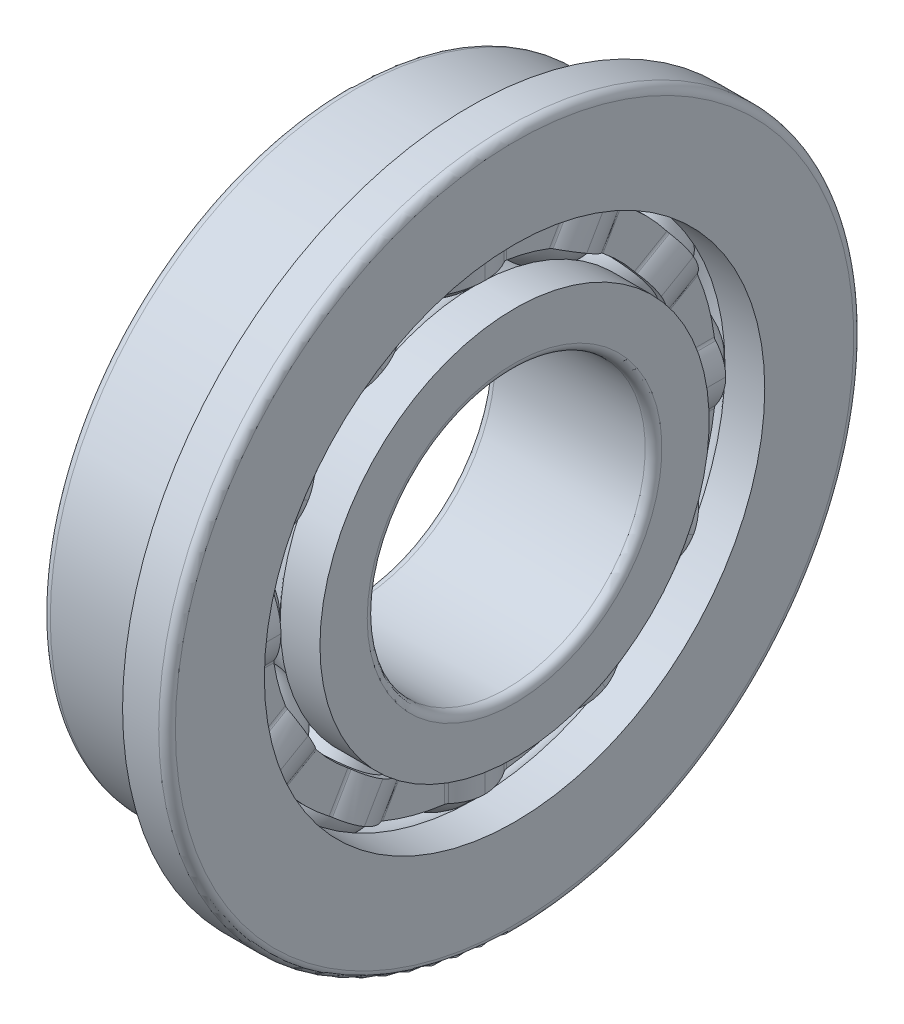
SolidWorks part; units mm, degrees
ref_plane "Front" through (0, 0, 0) normal (0, 0, 1) x (1, 0, 0)
ref_plane "Top" through (0, 0, 0) normal (0, 1, 0) x (1, 0, 0)
ref_plane "Right" through (0, 0, 0) normal (1, 0, 0) x (0, 0, -1)
sketch "Support-Front-Body" plane through (0, 0, 0) normal (0, 0, 1) x (1, 0, 0)
  line L0 (-1.5, 0) -> (1.5, 0) construction
  line L1 (1.5, 0) -> (1.5, 2.5) construction
  line L2 (-1.5, 0) -> (-1.5, 2.5) construction
  line L4 (-1.5, 5.5) -> (1.5, 5.5)
  line L5 (-1.5, 5.5) -> (-1.5, 4.5)
  line L6 (-1.5, 4.5) -> (1.5, 4.5)
  line L7 (1.5, 6.25) -> (1.5, 4.5)
  line L8 (-1.5, 3.5) -> (1.5, 3.5)
  line L9 (-1.5, 3.5) -> (-1.5, 2.5)
  line L10 (-1.5, 2.5) -> (1.5, 2.5)
  line L11 (1.5, 3.5) -> (1.5, 2.5)
  line L13 (-1.5, 4) -> (1.5, 4) construction
  line L14 (0, 0) -> (0, 2.5) construction
  line L15 (0, 2.5) -> (0, 3.5) construction
  line L16 (0, 3.5) -> (0, 4.5) construction
  line L17 (0, 4.5) -> (0, 5.5) construction
  line L19 (0.7, 6.25) -> (1.5, 6.25)
  line L20 (0.7, 6.25) -> (0.7, 5.5)
  dimension "Diam-Inner" = 5
  dimension "Diam-Outer" = 11
  dimension "CC-Ball" = 8
  dimension "Width-Inner" = 3
  dimension "Diam-Flange" = 12.5
  dimension "Width-Flange" = 0.8
sketch "Support-Front-Ball" plane through (0, 0, 0) normal (0, 0, 1) x (1, 0, 0)
  line L0 (-0.9, 4) -> (0.9, 4) construction
  line L1 (0, 0) -> (0, 3.1) construction
  line L2 (-1.5, 4) -> (1.5, 4) construction
  line L3 (0, 4) -> (0, 4.9) construction
  line L6 (0, 3.1) -> (0, 4) construction
  circle A0 centre (0, 4) radius 0.9
  dimension "Diam-Ball" = 1.8
sketch "Support-Front-Groove" plane through (0, 0, 0) normal (0, 0, 1) x (1, 0, 0)
  line L0 (0, 4.5) -> (0, 4.3333) construction
  line L1 (0, 4.3333) -> (0, 4.1667) construction
  line L2 (0, 4.1667) -> (0, 4) construction
  line L3 (-1.5, 4) -> (1.5, 4) construction
  line L4 (-0.9, 4) -> (0.9, 4) construction
  line L6 (-1.5, 4.5) -> (1.5, 4.5) construction
  line L7 (0, 3.1367) -> (0, 3.1) construction
  line L8 (0.7483, 3.5) -> (0.7851, 3.5) construction
  line L9 (-1.5, 3.5) -> (1.5, 3.5) construction
  line L11 (0, 0) -> (0, 3.1) construction
  line L12 (-0.9, 4) -> (0.9, 4) construction
  circle A0 centre (0, 4) radius 0.9 construction
  circle A1 centre (0, 4.1667) radius 1.0299
  circle A2 centre (0, 3.8333) radius 1.0299
sketch "Support-Front-Ball-Cage" plane through (0, 0, 0) normal (0, 0, 1) x (1, 0, 0)
  line L0 (0.9, 4) -> (-0.9644, 4) construction
  line L1 (-0.9644, 4.3333) -> (0.9644, 4.3333)
  line L2 (-0.9644, 4.3333) -> (-0.9644, 3.6667)
  line L3 (-0.9644, 3.6667) -> (0.9644, 3.6667)
  line L4 (0.9644, 4.3333) -> (0.9644, 3.6667)
  line L5 (-1.5, 4) -> (1.5, 4) construction
  line L6 (0, 3.6667) -> (0, 4.3333) construction
  line L7 (0, 3.5) -> (0, 4.5) construction
  line L8 (0.9, 4) -> (0.9644, 4) construction
  line L9 (0.9322, 4) -> (0.9322, 4.1667) construction
  line L10 (0.9322, 4.1667) -> (0.9322, 4.3333) construction
  line L11 (0.9322, 4.3333) -> (0.9322, 4.5) construction
  line L12 (-1.5, 4.5) -> (1.5, 4.5) construction
  line L13 (0.9644, 4.4167) -> (0.7977, 4.4167) construction
  line L14 (0, 4.3333) -> (0, 4.9644) construction
  circle A0 centre (0, 4) radius 0.9 construction
  circle A1 centre (0, 4) radius 0.9644 construction
  point P26 (0.9322, 4.4167)
sketch "Support-Right-Ball-Cage" plane through (0, 0, 0) normal (1, 0, 0) x (0, 0, -1)
  line L0 (0, 0) -> (0, 5.5) construction
  line L1 (0, 0) -> (-2.75, 4.7631) construction
  line L2 (0, 3.0356) -> (-1.5178, 2.6289) construction
  line L3 (-2.4822, 4.2993) -> (0, 4.9644) construction
  line L4 (0, 0) -> (-1.5205, 5.2857) construction
  line L6 (-1.3261, 5.3377) -> (0, 0) construction
  circle A0 centre (0, 0) radius 3.6667
  circle A1 centre (0, 0) radius 4.3333
  circle A2 centre (0, 4) radius 0.9644
  circle A3 centre (0, 0) radius 4 construction
  circle A4 centre (-2, 3.4641) radius 0.9644
  dimension "Angle-Ball" = 30
ref_plane "Ref-Plane-1" through (0, 2.8322, 0.7589) normal (0, 0.9659, 0.2588) x (-1, 0, 0)
sketch "Support-Ball-Gage-Inner" plane through (0, 2.8322, 0.7589) normal (0, 0.9659, 0.2588) x (-1, 0, 0)
  line L0 (-0.7955, -0.209) -> (-0.7955, 0.209)
  line L1 (0.7955, -0.209) -> (0.7955, 0.209)
  line L2 (0.9644, 0.7857) -> (0.9644, -0.7857)
  line L3 (-0.9644, 0) -> (-0.7955, 0) construction
  line L4 (-0.9, -1.0353) -> (-0.9, -0.209) construction
  line L5 (-0.9, -0.209) -> (-0.7955, -0.209) construction
  line L6 (-0.9, -0.209) -> (-0.9, -0.1045) construction
  line L7 (-0.9, -0.1045) -> (-0.9, 0) construction
  line L8 (-0.7955, 0) -> (0, 0) construction
  line L9 (-0.9644, 0.7857) -> (-0.9644, -0.7857)
  line L10 (-0.9644, -1.1215) -> (-0.9644, -0.949) construction
  line L11 (-0.9, -0.1045) -> (-0.7955, -0.209) construction
  line L12 (0, 0.7857) -> (0, -0.7857) construction
  arc A0 (-0.9644, -0.7857) -> (-0.812, -0.2654) centre (0, -0.7857) cw
  arc A1 (-0.812, -0.2654) -> (-0.7955, -0.209) centre (-0.9, -0.209) ccw
  arc A2 (-0.7955, 0.209) -> (-0.812, 0.2654) centre (-0.9, 0.209) ccw
  arc A3 (-0.812, 0.2654) -> (-0.9644, 0.7857) centre (0, 0.7857) cw
  arc A4 (0.812, 0.2654) -> (0.9644, 0.7857) centre (0, 0.7857) ccw
  arc A5 (0.7955, 0.209) -> (0.812, 0.2654) centre (0.9, 0.209) cw
  arc A6 (0.812, -0.2654) -> (0.7955, -0.209) centre (0.9, -0.209) cw
  arc A7 (0.9644, -0.7857) -> (0.812, -0.2654) centre (0, -0.7857) ccw
  dimension "D1" = 45
ref_plane "Ref-Plane-2" through (0, 4.6319, 1.2411) normal (0, -0.9659, -0.2588) x (1, 0, 0)
sketch "Support-Ball-Gage-Outer" plane through (0, 4.6319, 1.2411) normal (0, -0.9659, -0.2588) x (1, 0, 0)
  line L0 (0.9644, 1.2849) -> (0.9644, -1.2849)
  line L1 (0.7955, -0.7082) -> (0.7955, 0.7082)
  line L2 (0.9644, 0.7857) -> (0.9644, -0.7857) construction
  line L7 (0.7955, -0.209) -> (0.7955, 0.209) construction
  line L8 (0, 1.2849) -> (0, -1.2849) construction
  line L9 (-0.9644, 1.2849) -> (-0.9644, -1.2849)
  line L10 (-0.7955, -0.7082) -> (-0.7955, 0.7082)
  arc A0 (0.9644, -1.2849) -> (0.812, -0.7646) centre (0, -1.2849) ccw
  arc A1 (0.812, -0.7646) -> (0.7955, -0.7082) centre (0.9, -0.7082) cw
  arc A2 (0.7955, 0.7082) -> (0.812, 0.7646) centre (0.9, 0.7082) cw
  arc A3 (0.812, 0.7646) -> (0.9644, 1.2849) centre (0, 1.2849) ccw
  arc A4 (0.812, 0.2654) -> (0.7955, 0.209) centre (0.9, 0.209) ccw construction
  arc A5 (-0.812, -0.7646) -> (-0.7955, -0.7082) centre (-0.9, -0.7082) ccw
  arc A6 (-0.9644, -1.2849) -> (-0.812, -0.7646) centre (0, -1.2849) cw
  arc A7 (-0.812, 0.7646) -> (-0.9644, 1.2849) centre (0, 1.2849) cw
  arc A8 (-0.7955, 0.7082) -> (-0.812, 0.7646) centre (-0.9, 0.7082) ccw
ref_axis "Ref-Axis" through (-1.1, 0, 0) along (1, 0, 0)
ref_plane "Ref-Plane-Right" through (1.5, 0, 0) normal (1, 0, 0) x (0, 0, -1)
ref_plane "Ref-Plane-Left" through (-1.5, 0, 0) normal (1, 0, 0) x (0, 0, -1)
sketch "Sketch7" plane through (0, 0, 0) normal (0, 0, 1) x (1, 0, 0)
  line L0 (-0.9, 4) -> (0.9, 4) construction
  line L2 (-0.9, 4) -> (0.9, 4) construction
  line L4 (-0.9, 4) -> (0.9, 4)
  circle A0 centre (0, 4) radius 0.9 construction
  arc A1 (-0.9, 4) -> (0.9, 4) centre (0, 4) ccw
revolve "Body-Ball" add sketch "Sketch7" angle 360 about L2
sketch "Sketch10" plane through (0, 0, 0) normal (0, 0, 1) x (1, 0, 0)
  line L0 (-1.5, 0) -> (1.5, 0) construction
  line L1 (-0.9644, 4.3333) -> (-0.9644, 3.6667) construction
  line L2 (-0.9644, 4.3333) -> (0.9644, 4.3333) construction
  line L3 (0.9644, 4.3333) -> (0.9644, 3.6667) construction
  line L4 (-0.9644, 3.6667) -> (0.9644, 3.6667) construction
  line L5 (-1.5, 0) -> (1.5, 0) construction
  line L6 (-0.9644, 4.3333) -> (-0.9644, 3.6667)
  line L7 (-0.9644, 4.3333) -> (0.9644, 4.3333)
  line L8 (0.9644, 4.3333) -> (0.9644, 3.6667)
  line L9 (-0.9644, 3.6667) -> (0.9644, 3.6667)
revolve "Body-Ball-Cage" add sketch "Sketch10" angle 360 about L5
sketch "Sketch16" plane through (0, 2.8322, 0.7589) normal (0, 0.9659, 0.2588) x (-1, 0, 0)
  line L0 (0.7955, -0.209) -> (0.7955, 0.209) construction
  line L1 (0.9644, 0.7857) -> (0.9644, -0.7857) construction
  line L2 (0.7955, -0.209) -> (0.7955, 0.209)
  line L3 (0.9644, 0.7857) -> (0.9644, -0.7857)
  arc A0 (0.812, 0.2654) -> (0.9644, 0.7857) centre (0, 0.7857) ccw construction
  arc A1 (0.812, 0.2654) -> (0.7955, 0.209) centre (0.9, 0.209) ccw construction
  arc A2 (0.7955, -0.209) -> (0.812, -0.2654) centre (0.9, -0.209) ccw construction
  arc A3 (0.9644, -0.7857) -> (0.812, -0.2654) centre (0, -0.7857) ccw construction
  arc A4 (0.812, 0.2654) -> (0.9644, 0.7857) centre (0, 0.7857) ccw
  arc A5 (0.812, 0.2654) -> (0.7955, 0.209) centre (0.9, 0.209) ccw
  arc A6 (0.7955, -0.209) -> (0.812, -0.2654) centre (0.9, -0.209) ccw
  arc A7 (0.9644, -0.7857) -> (0.812, -0.2654) centre (0, -0.7857) ccw
sketch "Sketch17" plane through (0, 4.6319, 1.2411) normal (0, -0.9659, -0.2588) x (1, 0, 0)
  line L0 (-0.7955, -0.7082) -> (-0.7955, 0.7082) construction
  line L1 (-0.9644, 1.2849) -> (-0.9644, -1.2849) construction
  line L2 (-0.7955, -0.7082) -> (-0.7955, 0.7082)
  line L3 (-0.9644, 1.2849) -> (-0.9644, -1.2849)
  arc A0 (-0.9644, 1.2849) -> (-0.812, 0.7646) centre (0, 1.2849) ccw construction
  arc A1 (-0.7955, 0.7082) -> (-0.812, 0.7646) centre (-0.9, 0.7082) ccw construction
  arc A2 (-0.812, -0.7646) -> (-0.7955, -0.7082) centre (-0.9, -0.7082) ccw construction
  arc A3 (-0.812, -0.7646) -> (-0.9644, -1.2849) centre (0, -1.2849) ccw construction
  arc A4 (-0.9644, 1.2849) -> (-0.812, 0.7646) centre (0, 1.2849) ccw
  arc A5 (-0.7955, 0.7082) -> (-0.812, 0.7646) centre (-0.9, 0.7082) ccw
  arc A6 (-0.812, -0.7646) -> (-0.7955, -0.7082) centre (-0.9, -0.7082) ccw
  arc A7 (-0.812, -0.7646) -> (-0.9644, -1.2849) centre (0, -1.2849) ccw
loft "Cut-Ball-Cage-1" cut profiles "Sketch16", "Sketch17"
sketch "Sketch14" plane through (0, 2.8322, 0.7589) normal (0, 0.9659, 0.2588) x (-1, 0, 0)
  line L0 (-0.7955, -0.209) -> (-0.7955, 0.209) construction
  line L1 (-0.9644, 0.7857) -> (-0.9644, -0.7857) construction
  line L2 (-0.7955, -0.209) -> (-0.7955, 0.209)
  line L3 (-0.9644, 0.7857) -> (-0.9644, -0.7857)
  arc A0 (-0.9644, 0.7857) -> (-0.812, 0.2654) centre (0, 0.7857) ccw construction
  arc A1 (-0.7955, 0.209) -> (-0.812, 0.2654) centre (-0.9, 0.209) ccw construction
  arc A2 (-0.812, -0.2654) -> (-0.7955, -0.209) centre (-0.9, -0.209) ccw construction
  arc A3 (-0.812, -0.2654) -> (-0.9644, -0.7857) centre (0, -0.7857) ccw construction
  arc A4 (-0.9644, 0.7857) -> (-0.812, 0.2654) centre (0, 0.7857) ccw
  arc A5 (-0.7955, 0.209) -> (-0.812, 0.2654) centre (-0.9, 0.209) ccw
  arc A6 (-0.812, -0.2654) -> (-0.7955, -0.209) centre (-0.9, -0.209) ccw
  arc A7 (-0.812, -0.2654) -> (-0.9644, -0.7857) centre (0, -0.7857) ccw
sketch "Sketch15" plane through (0, 4.6319, 1.2411) normal (0, -0.9659, -0.2588) x (1, 0, 0)
  line L0 (0.7955, -0.7082) -> (0.7955, 0.7082) construction
  line L1 (0.9644, 1.2849) -> (0.9644, -1.2849) construction
  line L2 (0.7955, -0.7082) -> (0.7955, 0.7082)
  line L3 (0.9644, 1.2849) -> (0.9644, -1.2849)
  arc A0 (0.812, 0.7646) -> (0.9644, 1.2849) centre (0, 1.2849) ccw construction
  arc A1 (0.812, 0.7646) -> (0.7955, 0.7082) centre (0.9, 0.7082) ccw construction
  arc A2 (0.7955, -0.7082) -> (0.812, -0.7646) centre (0.9, -0.7082) ccw construction
  arc A3 (0.9644, -1.2849) -> (0.812, -0.7646) centre (0, -1.2849) ccw construction
  arc A4 (0.812, 0.7646) -> (0.9644, 1.2849) centre (0, 1.2849) ccw
  arc A5 (0.812, 0.7646) -> (0.7955, 0.7082) centre (0.9, 0.7082) ccw
  arc A6 (0.7955, -0.7082) -> (0.812, -0.7646) centre (0.9, -0.7082) ccw
  arc A7 (0.9644, -1.2849) -> (0.812, -0.7646) centre (0, -1.2849) ccw
loft "Cut-Ball-Cage-2" cut profiles "Sketch15", "Sketch14"
pattern_circular "Pattern-Ball" count 12 over 360 about axis through (-1.1, 0, 0) along (1, 0, 0) of "Body-Ball", "Cut-Ball-Cage-2", "Cut-Ball-Cage-1"
sketch "Sketch2" plane through (0, 0, 0) normal (0, 0, 1) x (1, 0, 0)
  line L4 (-1.5, 3.5) -> (-1.5, 2.5) construction
  line L5 (-1.5, 3.5) -> (1.5, 3.5) construction
  line L6 (1.5, 3.5) -> (1.5, 2.5) construction
  line L7 (-1.5, 2.5) -> (1.5, 2.5) construction
  line L8 (-1.5, 0) -> (1.5, 0) construction
  line L9 (-1.5, 0) -> (1.5, 0) construction
  line L10 (-1.5, 3.5) -> (-1.5, 2.5)
  line L11 (-1.5, 3.5) -> (-0.7851, 3.5)
  line L12 (1.5, 3.5) -> (1.5, 2.5)
  line L13 (-1.5, 2.5) -> (1.5, 2.5)
  line L14 (0.7851, 3.5) -> (1.5, 3.5)
  circle A1 centre (0, 4.1667) radius 1.0299 construction
  arc A2 (-0.7851, 3.5) -> (0.7851, 3.5) centre (0, 4.1667) ccw
sketch "Sketch8" plane through (0, 0, 0) normal (0, 0, 1) x (1, 0, 0)
  line L0 (-1.5, 0) -> (1.5, 0) construction
  line L1 (-1.5, 5.5) -> (-1.5, 4.5) construction
  line L2 (-1.5, 4.5) -> (1.5, 4.5) construction
  line L4 (-1.5, 0) -> (1.5, 0) construction
  line L5 (0.7, 6.25) -> (0.7, 5.5) construction
  line L6 (0.7, 6.25) -> (1.5, 6.25) construction
  line L8 (0.7, 6.25) -> (0.7, 5.5)
  line L10 (-1.5, 5.5) -> (-1.5, 4.5)
  line L11 (-1.5, 4.5) -> (-0.7851, 4.5)
  line L12 (1.5, 6.25) -> (1.5, 4.5) construction
  line L13 (-1.5, 5.5) -> (1.5, 5.5) construction
  line L14 (0.7851, 4.5) -> (1.5, 4.5)
  line L15 (0.7, 6.25) -> (1.5, 6.25)
  line L16 (1.5, 6.25) -> (1.5, 4.5)
  line L17 (-1.5, 5.5) -> (0.7, 5.5)
  circle A1 centre (0, 3.8333) radius 1.0299 construction
  arc A2 (0.7851, 4.5) -> (-0.7851, 4.5) centre (0, 3.8333) ccw
revolve "Body-Inner" add sketch "Sketch2" angle 360 about L9
revolve "Body-Outer" add sketch "Sketch8" angle 360 about L4
fillet "Cosmetic-Fillet-Outer-1" radius 0.15 1 edges at (-1.5, 0, 5.5)
fillet "Cosmetic-Fillet-Outer-2" radius 0.15 1 edges at (1.5, 0, 6.25)
fillet "Cosmetic-Fillet-Inner-1" radius 0.15 1 edges at (-1.5, 0, 2.5)
fillet "Cosmetic-Fillet-Inner-2" radius 0.15 1 edges at (1.5, 0, 2.5)
equation "\"Diam-Ball@Support-Front-Ball\"=(((\"Diam-Outer@Support-Front-Body\"-\"Diam-Inner@Support-Front-Body\")/2)*3)/5"
equation "\"Num-Ball@Pattern-Ball\"=INT((PI*(\"Diam-Outer@Support-Front-Body\"-((\"Diam-Outer@Support-Front-Body\"-\"Diam-Inner@Support-Front-Body\")/2)))/(\"Diam-Ball@Support-Front-Ball\"*1.2))"
equation "\"Angle-Ball@Support-Right-Ball-Cage\" = 360 / INT(((PI*(\"Diam-Outer@Support-Front-Body\"-((\"Diam-Outer@Support-Front-Body\"-\"Diam-Inner@Support-Front-Body\")/4)))/2)/\"Diam-Ball@Support-Front-Ball\")"
equation "\"Angle-Ball@Support-Right-Ball-Cage\" = 360 / \"Num-Ball@Pattern-Ball\""
